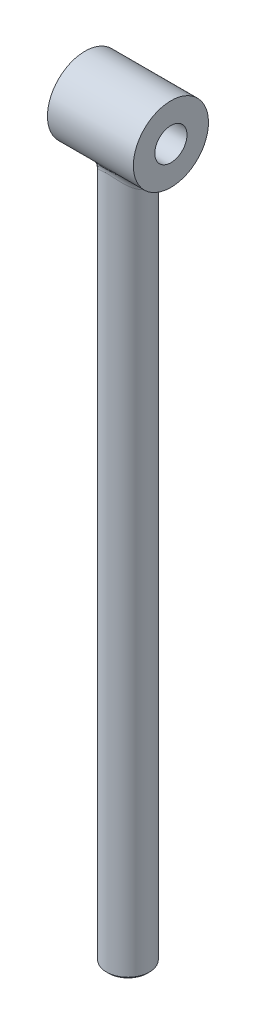
SolidWorks part; units mm, degrees
ref_plane "Front Plane" through (0, 0, 0) normal (0, 0, 1) x (1, 0, 0)
ref_plane "Top Plane" through (0, 0, 0) normal (0, 1, 0) x (1, 0, 0)
ref_plane "Right Plane" through (0, 0, 0) normal (1, 0, 0) x (0, 0, -1)
sketch "Sketch7" plane through (0, 1.1161, 0) normal (1, 0, 0) x (0, 0, -1)
  circle A0 centre (0, -1.1161) radius 17.5
  circle A1 centre (0, -1.1161) radius 7.5
  dimension "D1" = 35
  dimension "D2" = 15
extrude "Boss-Extrude3" add sketch "Sketch7" against normal blind 40 separate body
sketch "Sketch13" plane through (0.2416, 0, -0.9845) normal (0, -1, 0) x (1, 0, 0)
  line L0 (-40.2421, -16.5142) -> (-0.241, 18.4845) construction
  circle A0 centre (-20.2416, 0.9851) radius 10
  dimension "D1" = 20
extrude "Boss-Extrude4" add sketch "Sketch13" along normal blind 300 and the other way up to surface from offset 40 other way up to face at (-40, 0, -17.5)
fillet "Fillet2" radius 5 1 edges at (-20.203, -14.3628, 9.9979)
chamfer "Chamfer1" distance 1 angle 45 1 edges at (-20, -340, -10)
